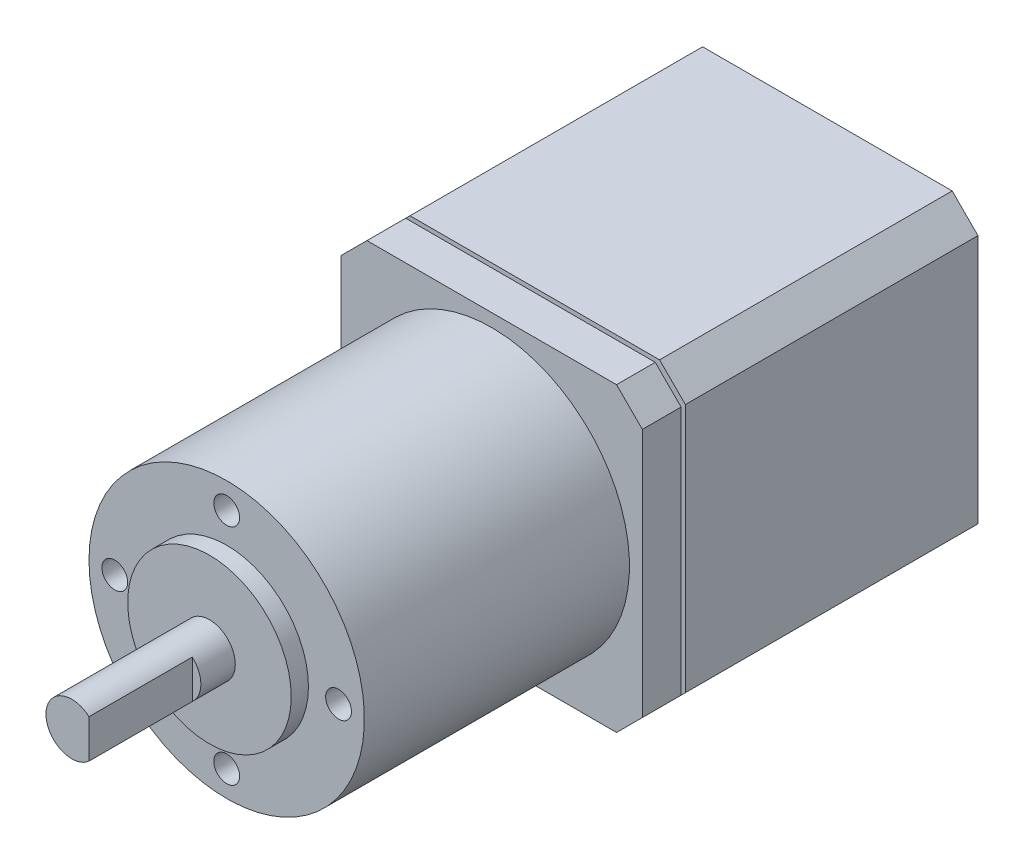
SolidWorks part; units mm, degrees
other "14HS13-0804S-PG19"
material "S235JR"
ref_plane "xy" through (0, 0, 0) normal (0, 0, 1) x (1, 0, 0)
ref_plane "xz" through (0, 0, 0) normal (0, 1, 0) x (1, 0, 0)
ref_plane "yz" through (0, 0, 0) normal (1, 0, 0) x (0, 0, -1)
ref_axis "x" through (-88.99, 0, 0) along (1, 0, 0)
ref_axis "y" through (0, 55, 0) along (0, -1, 0)
ref_axis "z" through (0, 0, -88.99) along (0, 0, 1)
sketch "Skizze1" plane through (0, 0, 0) normal (0, 0, 1) x (1, 0, 0)
  line L1 (-17.5, 17.5) -> (17.5, 17.5)
  line L2 (-17.5, 17.5) -> (-17.5, -17.5)
  line L3 (-17.5, -17.5) -> (17.5, -17.5)
  line L4 (17.5, 17.5) -> (17.5, -17.5)
  point P4 (0, 17.5)
  point P6 (-17.5, 0)
  dimension "D1" = 35
extrude "Aufsatz-Linear austragen1" add sketch "Skizze1" along normal blind 34
sketch "Skizze2" plane through (0, 0, 34) normal (0, 0, 1) x (1, 0, 0)
  circle A0 centre (0, 0) radius 16
  dimension "D1" = 32
extrude "Aufsatz-Linear austragen2" add sketch "Skizze2" along normal blind 35.8
sketch "Skizze3" plane through (0, 0, 69.8) normal (0, 0, 1) x (1, 0, 0)
  circle A0 centre (0, 0) radius 9.5
  dimension "D1" = 19
extrude "Aufsatz-Linear austragen3" add sketch "Skizze3" along normal blind 2
sketch "Skizze4" plane through (0, 0, 69.8) normal (0, 0, 1) x (1, 0, 0)
  circle A0 centre (0, 0) radius 3
  dimension "D1" = 6
extrude "Aufsatz-Linear austragen4" add sketch "Skizze4" along normal blind 18
sketch "Skizze5" plane through (0, 0, 69.8) normal (0, 0, 1) x (1, 0, 0)
  line L0 (-13, 0) -> (0, 13) construction
  line L1 (-13, 0) -> (0, -13) construction
  line L2 (0, 13) -> (13, 0) construction
  line L3 (0, -13) -> (13, 0) construction
  circle A0 centre (0, 0) radius 13 construction
  circle A1 centre (0, 13) radius 1.5
  circle A2 centre (13, 0) radius 1.5
  circle A3 centre (-13, 0) radius 1.5
  circle A4 centre (0, -13) radius 1.5
  dimension "D1" = 26
  dimension "D2" = 3
extrude "Schnitt-Linear austragen1" cut sketch "Skizze5" against normal blind 4
chamfer "Fase1" distance 3 angle 45 4 edges at (-17.5, -17.5, 17) (17.5, -17.5, 17) (-17.5, 17.5, 17) (17.5, 17.5, 17)
sketch "Skizze6" plane through (0, 0, 34) normal (0, 0, 1) x (1, 0, 0)
  line L8 (-17.5, 14.5) -> (-17.5, -14.5)
  line L9 (-17.5, -14.5) -> (-14.5, -17.5)
  line L10 (-14.5, -17.5) -> (14.5, -17.5)
  line L11 (14.5, -17.5) -> (17.5, -14.5)
  line L12 (17.5, -14.5) -> (17.5, 14.5)
  line L13 (17.5, 14.5) -> (14.5, 17.5)
  line L14 (14.5, 17.5) -> (-14.5, 17.5)
  line L15 (-14.5, 17.5) -> (-17.5, 14.5)
  line L16 (-17.5, 14.5) -> (-17.5, -14.5)
  line L17 (-17.5, -14.5) -> (-14.5, -17.5)
  line L18 (-14.5, -17.5) -> (14.5, -17.5)
  line L19 (14.5, -17.5) -> (17.5, -14.5)
  line L20 (17.5, -14.5) -> (17.5, 14.5)
  line L21 (17.5, 14.5) -> (14.5, 17.5)
  line L22 (14.5, 17.5) -> (-14.5, 17.5)
  line L23 (-14.5, 17.5) -> (-17.5, 14.5)
  dimension "D1" = 0
extrude "Aufsatz-Linear austragen5" add sketch "Skizze6" along normal blind 4.5 from offset 0.5
sketch "Skizze7" plane through (0, 0, 87.8) normal (0, 0, 1) x (1, 0, 0)
  line L0 (2, 2.2361) -> (2, -2.2361)
  arc A0 (2, 2.2361) -> (2, -2.2361) centre (0, 0) cw
  circle A1 centre (0, 0) radius 3 construction
  point P6 (3, 0)
  dimension "D1" = 1
extrude "Schnitt-Linear austragen2" cut sketch "Skizze7" against normal blind 12
